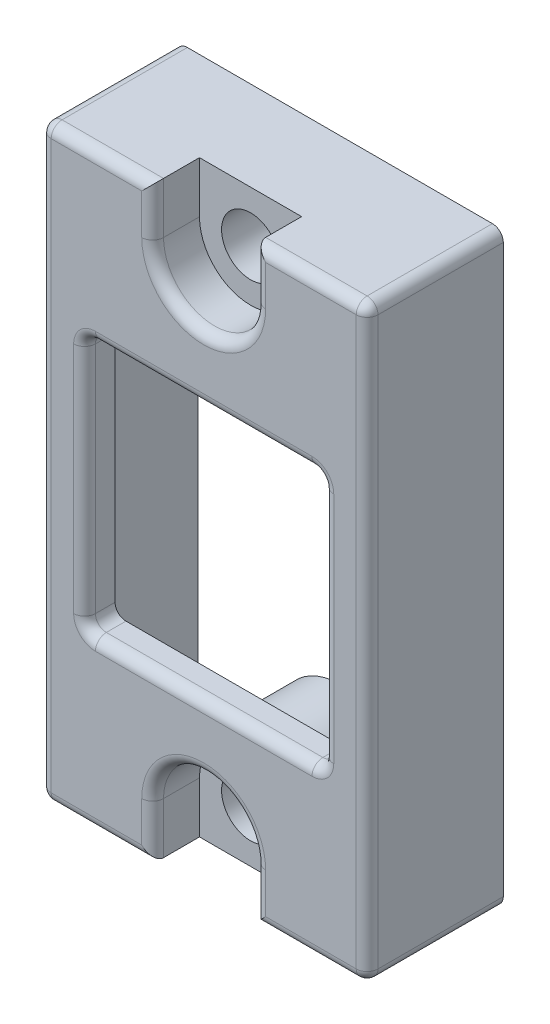
SolidWorks part; units mm, degrees
material "Nylon 101"
ref_plane "Front Plane" through (0, 0, 0) normal (0, 0, 1) x (1, 0, 0)
ref_plane "Top Plane" through (0, 0, 0) normal (0, 1, 0) x (1, 0, 0)
ref_plane "Right Plane" through (0, 0, 0) normal (1, 0, 0) x (0, 0, -1)
sketch "Sketch1" plane through (0, 0, 0) normal (0, 0, 1) x (1, 0, 0)
  line L0 (73.66, -84.3122) -> (66.04, -84.3122) construction
  line L2 (81.28, -96.5042) -> (81.28, -72.1202)
  line L3 (81.28, -96.5042) -> (81.28, -98.0282)
  line L4 (66.04, -96.5042) -> (66.04, -72.1202)
  line L5 (81.28, -96.5042) -> (66.04, -72.1202) construction
  line L6 (81.28, -72.1202) -> (66.04, -96.5042) construction
  line L7 (66.04, -96.5042) -> (66.04, -98.0282)
  line L8 (66.04, -72.1202) -> (66.04, -70.5962)
  line L9 (66.04, -70.5962) -> (81.28, -70.5962)
  line L10 (81.28, -72.1202) -> (81.28, -70.5962)
  line L11 (66.04, -72.1202) -> (81.28, -70.5962) construction
  line L12 (66.04, -70.5962) -> (81.28, -72.1202) construction
  line L13 (66.04, -98.0282) -> (81.28, -98.0282)
  point P4 (73.66, -84.3122)
  point P10 (73.66, -71.3582)
  dimension "D1" = 1.524
extrude "Boss-Extrude1" add sketch "Sketch1" along normal blind 6.35
sketch "Sketch2" plane through (0, 0, 6.35) normal (0, 0, 1) x (1, 0, 0)
  line L5 (68.1037, -78.3591) -> (68.1037, -90.2654)
  line L6 (79.2162, -78.3591) -> (68.1037, -78.3591)
  line L7 (79.2162, -90.2654) -> (79.2162, -78.3591)
  line L8 (68.1037, -90.2654) -> (79.2162, -90.2654)
  line L9 (68.1037, -78.3591) -> (68.1037, -90.2654)
  line L10 (79.2162, -78.3591) -> (68.1037, -78.3591)
  line L11 (79.2162, -90.2654) -> (79.2162, -78.3591)
  line L12 (68.1037, -90.2654) -> (79.2162, -90.2654)
  dimension "D1" = 0
extrude "Cut-Extrude1" cut sketch "Sketch2" against normal through all
shell "Shell1" thickness 1 removed face at (73.66, -84.3122, 0) removed face at (73.66, -78.3591, 3.175) removed face at (79.2162, -84.3122, 3.175) removed face at (73.66, -90.2654, 3.175) removed face at (68.1037, -84.3122, 3.175)
sketch "Sketch5" plane through (0, 0, 0) normal (0, 0, -1) x (-1, 0, 0)
  line L0 (-73.66, -98.0282) -> (-73.66, -70.5962) construction
  line L1 (-66.04, -98.0282) -> (-81.28, -98.0282) construction
  line L2 (-81.28, -70.5962) -> (-66.04, -70.5962) construction
  line L3 (-70.7724, -76.3714) -> (-70.7724, -70.5962)
  line L4 (-81.28, -98.0282) -> (-81.28, -70.5962) construction
  line L5 (-81.28, -84.3122) -> (-73.66, -84.3122) construction
  line L6 (-76.5476, -92.253) -> (-70.7724, -92.253)
  line L7 (-76.5476, -92.253) -> (-76.5476, -98.0282)
  line L8 (-76.5476, -98.0282) -> (-70.7724, -98.0282)
  line L9 (-70.7724, -92.253) -> (-70.7724, -98.0282)
  line L10 (-76.5476, -92.253) -> (-70.7724, -98.0282) construction
  line L11 (-76.5476, -98.0282) -> (-70.7724, -92.253) construction
  line L12 (-76.5476, -76.3714) -> (-70.7724, -76.3714)
  line L13 (-76.5476, -76.3714) -> (-76.5476, -70.5962)
  line L14 (-76.5476, -70.5962) -> (-70.7724, -70.5962)
  point P6 (-73.66, -95.1406)
  dimension "D1" = 5.7752
extrude "Boss-Extrude2" add sketch "Sketch5" against normal through all
hole_wizard "CBORE for #2 Socket Head Cap Screw2" positions "Sketch4" profile "Sketch3" counterbore size "#2" standard "ANSI Inch" end condition through all
sketch "Sketch4" plane through (0, 0, 6.35) normal (0, 0, 1) x (1, 0, 0)
  line L0 (73.66, -70.5962) -> (73.66, -98.0282) construction
  line L1 (81.28, -70.5962) -> (66.04, -70.5962) construction
  line L2 (66.04, -98.0282) -> (81.28, -98.0282) construction
  line L3 (73.66, -84.3122) -> (81.28, -84.3122) construction
  line L4 (81.28, -98.0282) -> (81.28, -70.5962) construction
  point P0 (73.66, -95.6406)
  point P23 (73.66, -72.9838)
  dimension "D1" = 2.3876
sketch "Sketch3" plane through (73.66, -95.6406, 6.35) normal (1, 0, 0) x (0, -1, 0)
  line L0 (0, 0) -> (0, 6.35)
  line L1 (0, 6.35) -> (1.3525, 6.35)
  line L3 (1.3525, 6.35) -> (1.3525, 2.1844)
  line L4 (1.3525, 2.1844) -> (2.3812, 2.1844)
  line L5 (2.3812, 2.1844) -> (2.3812, 0)
  line L7 (2.3812, 0) -> (0, 0)
  line L11 (0, -6.35) -> (0, 107.95) construction
  dimension "Thru Hole Dia." = 2.7051
  dimension "Thru Hole Depth" = 6.35
  dimension "C'Bore Dia." = 4.7625
  dimension "C'Bore Depth" = 2.1844
sketch "Sketch6" plane through (0, 0, 0) normal (0, 0, -1) x (-1, 0, 0)
  line L0 (-76.5476, -92.253) -> (-76.5476, -97.0282) construction
  line L1 (-76.5476, -95.6406) -> (-76.8016, -95.6406)
  line L2 (-76.8016, -95.6406) -> (-76.8016, -92.253)
  line L3 (-76.8016, -92.253) -> (-70.5184, -92.253)
  line L4 (-70.7724, -92.253) -> (-76.5476, -92.253) construction
  line L5 (-73.66, -95.6406) -> (-73.66, -92.753) construction
  line L6 (-70.7724, -95.6406) -> (-70.5184, -95.6406)
  line L7 (-70.5184, -95.6406) -> (-70.5184, -92.253)
  line L8 (-79.2162, -84.3122) -> (-68.1037, -84.3122) construction
  line L9 (-79.2162, -90.2654) -> (-79.2162, -78.3591) construction
  line L10 (-68.1037, -78.3591) -> (-68.1037, -90.2654) construction
  line L11 (-76.8016, -72.9838) -> (-76.8016, -76.3714)
  line L12 (-76.5476, -72.9838) -> (-76.8016, -72.9838)
  line L13 (-70.7724, -72.9838) -> (-70.5184, -72.9838)
  line L14 (-70.5184, -72.9838) -> (-70.5184, -76.3714)
  line L15 (-76.8016, -76.3714) -> (-70.5184, -76.3714)
  arc A1 (-70.7724, -95.6406) -> (-76.5476, -95.6406) centre (-73.66, -95.6406) ccw
  arc A2 (-70.7724, -72.9838) -> (-76.5476, -72.9838) centre (-73.66, -72.9838) cw
  point P15 (-73.66, -92.253)
  dimension "D1" = 0.254
extrude "Cut-Extrude2" cut sketch "Sketch6" against normal offset from surface (4.9276 mm away) 1.4224 up to face at (76.0413, -95.6406, 6.35)
sketch "Sketch7" plane through (0, 0, 5.35) normal (0, 0, -1) x (-1, 0, 0)
  line L4 (-79.2162, -90.2654) -> (-68.1037, -90.2654)
  line L5 (-79.2162, -78.3591) -> (-79.2162, -90.2654)
  line L6 (-68.1037, -78.3591) -> (-79.2162, -78.3591)
  line L7 (-68.1037, -90.2654) -> (-68.1037, -78.3591)
  line L8 (-79.2162, -90.2654) -> (-68.1037, -90.2654)
  line L9 (-79.2162, -78.3591) -> (-79.2162, -90.2654)
  line L10 (-68.1037, -78.3591) -> (-79.2162, -78.3591)
  line L11 (-68.1037, -90.2654) -> (-68.1037, -78.3591)
  line L12 (-70.7724, -76.3714) -> (-76.5476, -76.3714)
  line L13 (-76.5476, -76.3714) -> (-76.5476, -71.5962)
  line L14 (-76.5476, -71.5962) -> (-80.28, -71.5962)
  line L15 (-80.28, -71.5962) -> (-80.28, -97.0282)
  line L16 (-80.28, -97.0282) -> (-76.5476, -97.0282)
  line L17 (-76.5476, -97.0282) -> (-76.5476, -92.253)
  line L18 (-76.5476, -92.253) -> (-70.7724, -92.253)
  line L19 (-70.7724, -92.253) -> (-70.7724, -97.0282)
  line L20 (-70.7724, -97.0282) -> (-67.04, -97.0282)
  line L21 (-67.04, -97.0282) -> (-67.04, -71.5962)
  line L22 (-67.04, -71.5962) -> (-70.7724, -71.5962)
  line L23 (-70.7724, -71.5962) -> (-70.7724, -76.3714)
  line L24 (-70.7724, -76.3714) -> (-76.5476, -76.3714)
  line L25 (-76.5476, -76.3714) -> (-76.5476, -71.5962)
  line L26 (-76.5476, -71.5962) -> (-80.28, -71.5962)
  line L27 (-80.28, -71.5962) -> (-80.28, -97.0282)
  line L28 (-80.28, -97.0282) -> (-76.5476, -97.0282)
  line L29 (-76.5476, -97.0282) -> (-76.5476, -92.253)
  line L30 (-76.5476, -92.253) -> (-70.7724, -92.253)
  line L31 (-70.7724, -92.253) -> (-70.7724, -97.0282)
  line L32 (-70.7724, -97.0282) -> (-67.04, -97.0282)
  line L33 (-67.04, -97.0282) -> (-67.04, -71.5962)
  line L34 (-67.04, -71.5962) -> (-70.7724, -71.5962)
  line L35 (-70.7724, -71.5962) -> (-70.7724, -76.3714)
  dimension "D1" = 0
  dimension "D2" = 0
extrude "Boss-Extrude4" add sketch "Sketch7" along normal up to surface (0.4224 mm away) up to face at (73.66, -75.3995, 4.9276)
sketch "Sketch8" plane through (0, 0, 6.35) normal (0, 0, 1) x (1, 0, 0)
  line L0 (66.04, -98.0282) -> (81.28, -98.0282) construction
  line L1 (71.2788, -95.6406) -> (76.0413, -95.6406)
  line L2 (71.2788, -95.6406) -> (71.2788, -98.0282)
  line L3 (71.2788, -98.0282) -> (76.0413, -98.0282)
  line L4 (76.0413, -95.6406) -> (76.0413, -98.0282)
  line L5 (71.2788, -95.6406) -> (76.0413, -98.0282) construction
  line L6 (71.2788, -98.0282) -> (76.0413, -95.6406) construction
  line L7 (68.1037, -84.3122) -> (79.2162, -84.3122) construction
  line L8 (68.1037, -78.3591) -> (68.1037, -90.2654) construction
  line L9 (79.2162, -90.2654) -> (79.2162, -78.3591) construction
  line L10 (71.2788, -72.9838) -> (71.2788, -70.5962)
  line L11 (71.2788, -70.5962) -> (76.0413, -70.5962)
  line L12 (76.0413, -72.9838) -> (76.0413, -70.5962)
  line L13 (71.2788, -72.9838) -> (76.0413, -72.9838)
  circle A0 centre (73.66, -95.6406) radius 2.3813 construction
  point P4 (73.66, -96.8344)
  point P7 (73.66, -95.6406)
extrude "Cut-Extrude3" cut sketch "Sketch8" against normal up to surface (2.1844 mm away) up to face at (75.0125, -95.6406, 4.1656)
fillet "Fillet1" radius 0.508 24 edges at (79.2162, -84.3122, 6.35) (73.66, -78.3591, 6.35) (68.1037, -84.3122, 6.35) (73.66, -90.2654, 6.35) (78.6606, -70.5962, 6.35) (81.28, -84.3122, 6.35) (78.6606, -98.0282, 6.35) (76.0413, -96.8344, 6.35) (73.66, -93.2594, 6.35) (71.2788, -96.8344, 6.35) (68.6594, -98.0282, 6.35) (66.04, -84.3122, 6.35) (68.6594, -70.5962, 6.35) (71.2788, -71.79, 6.35) (73.66, -75.3651, 6.35) (76.0413, -71.79, 6.35) (66.04, -98.0282, 3.175) (66.04, -70.5962, 3.175) (81.28, -70.5962, 3.175) (81.28, -98.0282, 3.175) (68.1037, -78.3591, 5.6388) (79.2162, -78.3591, 5.6388) (79.2162, -90.2654, 5.6388) (68.1037, -90.2654, 5.6388)
